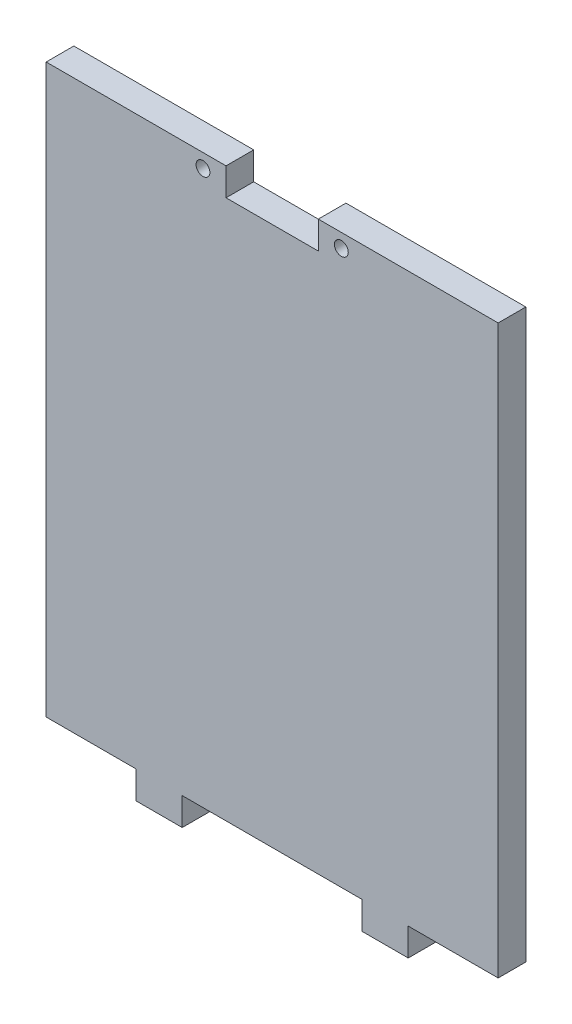
SolidWorks part; units mm, degrees
ref_plane "Plan de face" through (0, 0, 0) normal (0, 0, 1) x (1, 0, 0)
ref_plane "Plan de dessus" through (0, 0, 0) normal (0, 1, 0) x (1, 0, 0)
ref_plane "Plan de droite" through (0, 0, 0) normal (1, 0, 0) x (0, 0, -1)
sketch "Esquisse1" plane through (0, 0, 0) normal (0, 0, 1) x (1, 0, 0)
  line L0 (0, 176.8395) -> (0, -221.1538) construction
  line L1 (-49, 61.5) -> (49, 61.5)
  line L2 (-49, 61.5) -> (-49, -61.5)
  line L3 (-49, -61.5) -> (49, -61.5)
  line L4 (49, 61.5) -> (49, -61.5)
  line L5 (376.8436, 0) -> (-286.1998, 0) construction
  line L6 (-376.8436, 0) -> (286.1998, 0) construction
  dimension "D1" = 123
  dimension "D2" = 98
  dimension "D3" = 49
  dimension "D4" = 61.5
extrude "Boss.-Extru.1" add sketch "Esquisse1" along normal blind 6
sketch "Esquisse2" plane through (0, 0, 6) normal (0, 0, 1) x (1, 0, 0)
  line L1 (-49, -61.5) -> (49, -61.5) construction
  line L2 (29.5, -61.5) -> (19.5, -61.5)
  line L3 (29.5, -61.5) -> (29.5, -67.5)
  line L4 (29.5, -67.5) -> (19.5, -67.5)
  line L6 (154.6429, 0) -> (-167.6281, 0) construction
  line L7 (19.5, -61.5) -> (19.5, -67.5)
  line L8 (-49, 61.5) -> (-49, -61.5) construction
  line L9 (-19.5, -61.5) -> (-29.5, -61.5)
  line L10 (-19.5, -61.5) -> (-19.5, -67.5)
  line L11 (-19.5, -67.5) -> (-29.5, -67.5)
  line L12 (-29.5, -61.5) -> (-29.5, -67.5)
  dimension "D1" = 6
  dimension "D2" = 6
  dimension "D3" = 10
  dimension "D4" = 10
  dimension "D5" = 19.5
  dimension "D6" = 39
extrude "Boss.-Extru.2" add sketch "Esquisse2" against normal blind 6
sketch "Esquisse3" plane through (0, 0, 6) normal (0, 0, 1) x (1, 0, 0)
  line L0 (-49, 61.5) -> (-49, -61.5) construction
  line L2 (84.5882, 58.5) -> (-34.9143, 58.5) construction
  line L4 (49, -61.5) -> (49, 61.5) construction
  line L5 (49, 61.5) -> (-49, 61.5) construction
  circle A0 centre (-15, 58.5) radius 1.5
  circle A3 centre (15, 58.5) radius 1.5
  dimension "D1" = 3
  dimension "D2" = 3
  dimension "D3" = 34
  dimension "D4" = 34
  dimension "D5" = 3
extrude "Enlèv. mat.-Extru.1" cut sketch "Esquisse3" against normal blind 6
sketch "Esquisse4" plane through (0, 0, 6) normal (0, 0, 1) x (1, 0, 0)
  line L0 (49, 61.5) -> (-49, 61.5) construction
  line L1 (-10, 61.5) -> (10, 61.5)
  line L2 (-10, 61.5) -> (-10, 55.5)
  line L3 (-10, 55.5) -> (10, 55.5)
  line L4 (10, 61.5) -> (10, 55.5)
  line L5 (49, -61.5) -> (49, 61.5) construction
  dimension "D1" = 6
  dimension "D2" = 20
  dimension "D3" = 39
extrude "Enlèv. mat.-Extru.2" cut sketch "Esquisse4" against normal blind 6
equation "\"D3@Esquisse1\"=\"D2@Esquisse1\"/2"
equation "\"D4@Esquisse1\"=\"D1@Esquisse1\"/2"
